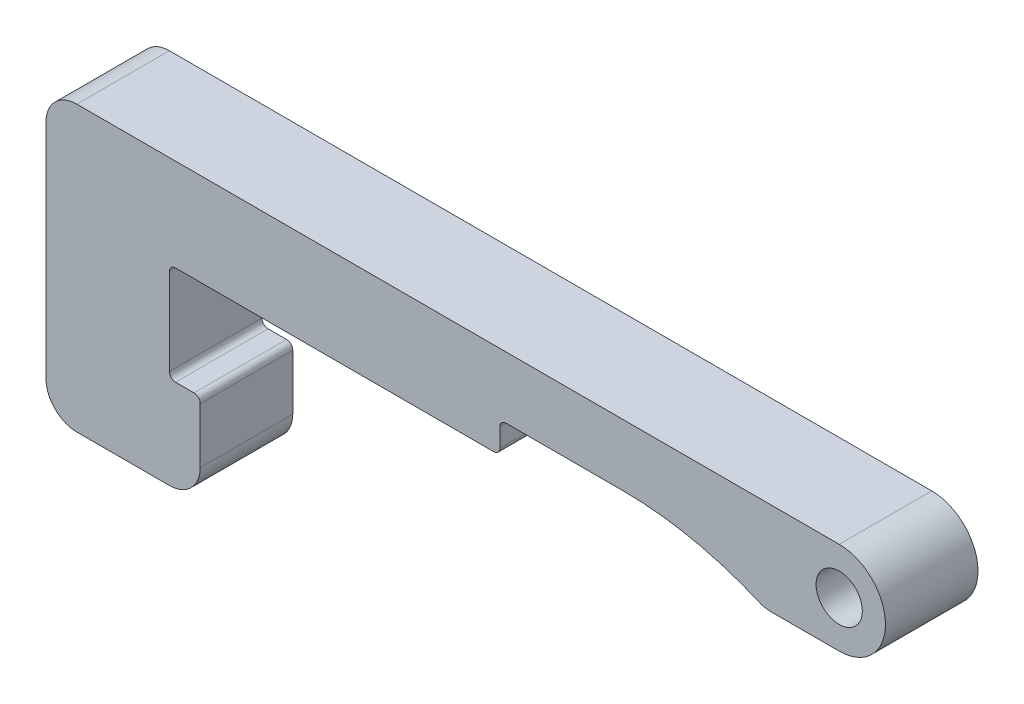
SolidWorks part; units mm, degrees
ref_plane "Front Plane" through (0, 0, 0) normal (0, 0, 1) x (1, 0, 0)
ref_plane "Top Plane" through (0, 0, 0) normal (0, 1, 0) x (1, 0, 0)
ref_plane "Right Plane" through (0, 0, 0) normal (1, 0, 0) x (0, 0, -1)
sketch "Sketch1" plane through (0, 0, 0) normal (0, 0, 1) x (1, 0, 0)
  line L0 (50, 0) -> (0, 0)
  line L1 (0, 0) -> (0, 92.063)
  line L2 (0, 92.063) -> (257.156, 92.063)
  line L4 (257.156, 62.063) -> (232.9664, 62.063)
  line L5 (147.1625, 62.063) -> (40, 62.063)
  line L6 (40, 62.063) -> (40, 30)
  line L7 (40, 30) -> (50, 30)
  line L8 (50, 30) -> (50, 0)
  line L9 (147.1625, 62.063) -> (147.1625, 72.063)
  line L10 (147.1625, 72.063) -> (186.7076, 72.063)
  arc A1 (232.9664, 62.063) -> (186.7076, 72.063) centre (186.7076, -39.9309) ccw
  circle A3 centre (257.156, 77.063) radius 7.5
  arc A4 (257.156, 62.063) -> (257.156, 92.063) centre (257.156, 77.063) ccw
  point P3 (0, 0)
  point P7 (0, 0)
  point P10 (259.8909, 73.9216)
  point P11 (196.9574, 82.1312)
  point P18 (297.1173, 121.9644)
  point P19 (225.9756, 75.3025)
  point P20 (0, 0)
  point P21 (186.7076, 71.6613)
  point P22 (232.9664, 64.1685)
  point P25 (257.156, 77.063)
  dimension "D5" = 15
  dimension "D6" = 30
  dimension "D1" = 40
  dimension "D2" = 10
  dimension "D3" = 30
  dimension "D4" = 30
  dimension "D7" = 10
extrude "Boss-Extrude1" add sketch "Sketch1" along normal blind 30
fillet "Fillet1" radius 10 4 edges at (232.9664, 62.063, 15) (0, 92.063, 15) (50, 0, 15) (0, 0, 15)
fillet "Fillet2" radius 2 5 edges at (147.1625, 72.063, 15) (147.1625, 62.063, 15) (40, 62.063, 15) (40, 30, 15) (50, 30, 15)
